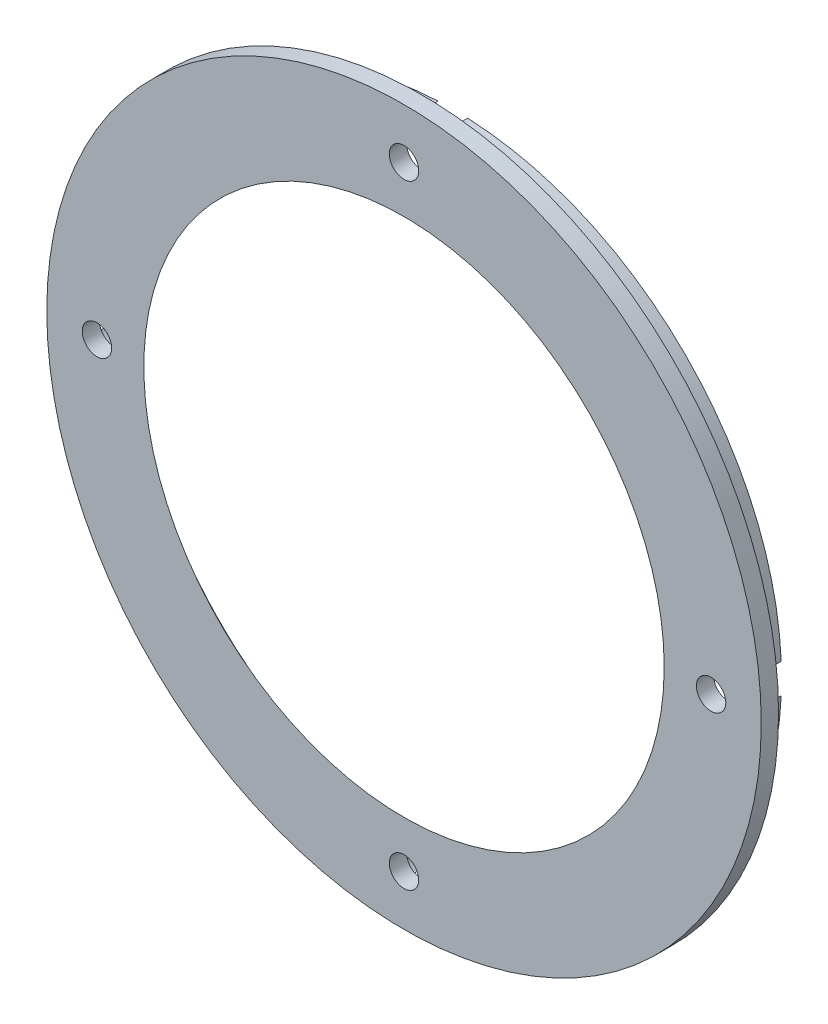
SolidWorks part; units mm, degrees
ref_plane "Front Plane" through (0, 0, 0) normal (0, 0, 1) x (1, 0, 0)
ref_plane "Top Plane" through (0, 0, 0) normal (0, 1, 0) x (1, 0, 0)
ref_plane "Right Plane" through (0, 0, 0) normal (1, 0, 0) x (0, 0, -1)
sketch "Sketch2" plane through (0, 0, 0) normal (0, 1, 0) x (1, 0, 0)
  line L0 (-21.1656, -4) -> (-21.1656, 4)
  line L1 (-9.9458, -4) -> (-21.1656, 4)
  line L2 (20.1344, -4) -> (20.1344, 1.8849)
  line L3 (-21.1656, -4) -> (20.1344, -4)
revolve "Revolve1" add sketch "Sketch2" angle 360 about L2 region at (-17.4256, 0, 1.3333)
sketch "Sketch3" plane through (0, 0, 4) normal (0, 0, 1) x (1, 0, 0)
  circle A0 centre (20.1344, 35.5) radius 3
  circle A1 centre (20.1344, 0) radius 30.0802
  arc A2 (-21.257, 3) -> (-21.257, -3) centre (20.1344, 0) ccw
  arc A3 (-15.3656, -3) -> (-15.3656, 3) centre (-15.3656, 0) ccw
  circle A14 centre (20.1344, 0) radius 41.5
  circle A15 centre (-15.3656, 0) radius 3
  circle A16 centre (55.6344, 0) radius 3
  circle A17 centre (20.1344, -35.5) radius 3
  point P19 (20.1344, 0)
  dimension "D1" = 4
extrude "Cut-Extrude1" cut sketch "Sketch3" against normal through all contours A0 | A16 | A17 | A15 region at (20.1344, 35.5, 4) region at (55.6344, 0, 4) region at (20.1344, -35.5, 4)
sketch "Sketch4" plane through (0, 0, 4) normal (0, 0, 1) x (1, 0, 0)
  circle A0 centre (20.1344, 0) radius 38
  circle A1 centre (20.1344, 0) radius 41.3 construction
  circle A2 centre (20.1344, 0) radius 41.3
  circle A4 centre (20.1344, 0) radius 30.0802
  circle A5 centre (20.1344, 0) radius 30.0802
  circle A6 centre (-15.3656, 0) radius 3
  circle A7 centre (-15.3656, 0) radius 3
  circle A8 centre (20.1344, -35.5) radius 3
  circle A9 centre (20.1344, -35.5) radius 3
  circle A10 centre (55.6344, 0) radius 3
  circle A11 centre (55.6344, 0) radius 3
  circle A12 centre (20.1344, 35.5) radius 3
  circle A13 centre (20.1344, 35.5) radius 3
  circle M1 centre (20.1344, 35.5) radius 3
  circle M2 centre (55.6344, 0) radius 3
  circle M3 centre (20.1344, -35.5) radius 3
  circle M4 centre (-15.3656, 0) radius 3
  circle M6 centre (20.1344, 0) radius 41.3
  dimension "D1" = 0
  dimension "D2" = 0
  dimension "D3" = 0
  dimension "D4" = 0
  dimension "D5" = 0
extrude "Cut-Extrude2" cut sketch "Sketch4" against normal blind 10 contours A0 M6 M2 M3 M4 M1 region at (-19.9974, 0, 4)
extrude "Boss-Extrude1" add sketch "Sketch4<3>" against normal blind 2 contours A0 M6 M2 M3 M4 M1 region at (-19.9974, 0, 4)
sketch "Sketch4<3>" plane through (0, 0, 4) normal (0, 0, 1) x (1, 0, 0) same geometry as "Sketch4"
sketch "Sketch5" plane through (0, 0, 4) normal (0, 0, 1) x (1, 0, 0)
  circle A0 centre (20.1344, 35.5) radius 1.7
  circle A3 centre (20.1344, -35.5) radius 3
  circle A4 centre (20.1344, -35.5) radius 3
  circle A5 centre (-15.3656, 0) radius 3
  circle A6 centre (-15.3656, 0) radius 3
  circle A7 centre (20.1344, 35.5) radius 3
  circle A8 centre (20.1344, 35.5) radius 3
  circle A9 centre (55.6344, 0) radius 3
  circle A10 centre (55.6344, 0) radius 3
  circle A11 centre (55.6344, 0) radius 1.7
  circle A12 centre (-15.3656, 0) radius 1.7
  circle A13 centre (20.1344, -35.5) radius 1.7
  dimension "D2" = 0
  dimension "D3" = 0
  dimension "D4" = 0
  dimension "D5" = 0
extrude "Boss-Extrude2" add sketch "Sketch5" against normal blind 2
